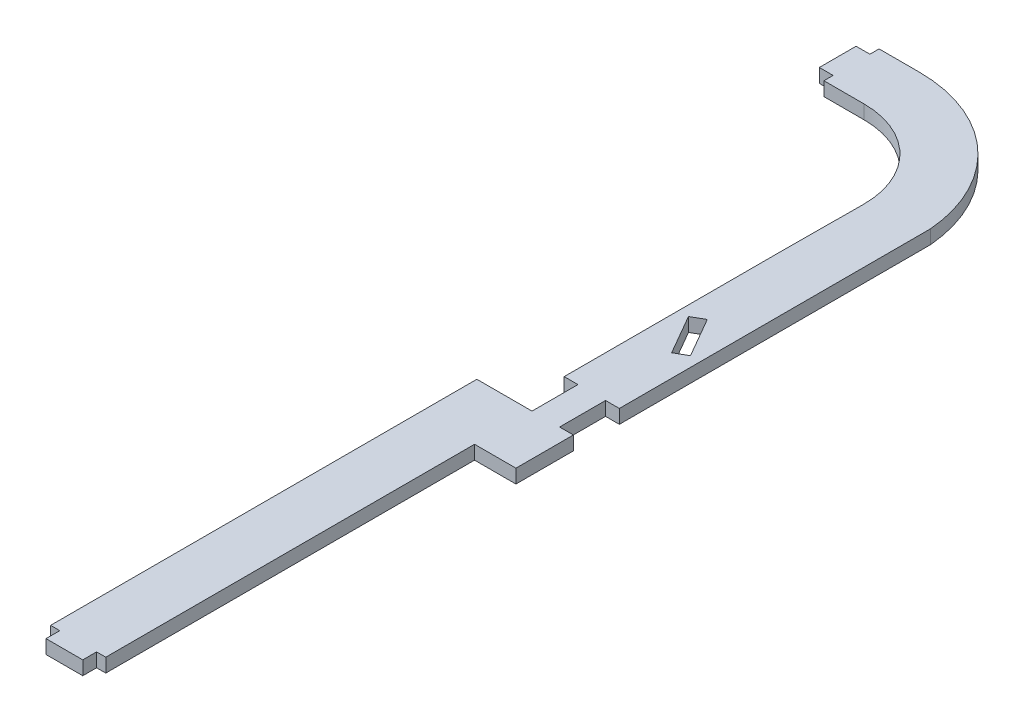
SolidWorks part; units mm, degrees
ref_plane "Alzado" through (0, 0, 0) normal (0, 0, 1) x (1, 0, 0)
ref_plane "Planta" through (0, 0, 0) normal (0, 1, 0) x (1, 0, 0)
ref_plane "Vista lateral" through (0, 0, 0) normal (1, 0, 0) x (0, 0, -1)
sketch "Croquis1" plane through (0, 0, 0) normal (0, 1, 0) x (1, 0, 0)
  line L0 (37.51, 4) -> (34.51, 4)
  line L1 (34.51, 0) -> (34.51, 8)
  line L2 (34.51, 8) -> (37.51, 8)
  line L3 (37.51, 8) -> (37.51, 10)
  line L4 (77, -108.5) -> (77, -96) construction
  line L5 (72.5, 3.893) -> (72.5, -188.737) construction
  line L6 (65, -38.5334) -> (65.107, -20.8557)
  line L7 (37.51, 10) -> (46.2513, 10)
  line L8 (37.51, -2) -> (46.2513, -2)
  line L9 (37.51, 0) -> (37.51, -2)
  line L10 (56, -188.737) -> (58, -188.737)
  line L11 (77, -108.5) -> (77, -96)
  line L12 (66, -191.737) -> (58, -191.737)
  line L13 (58, -191.737) -> (58, -188.737)
  line L14 (34.51, 0) -> (37.51, 0)
  line L15 (66, -191.737) -> (66, -188.737)
  line L16 (66, -188.737) -> (68, -188.737)
  line L17 (56, -188.737) -> (56, -96)
  line L18 (77, 4) -> (37.51, 4) construction
  line L19 (71, 3.893) -> (46.2513, -20.8557) construction
  line L20 (56, -96) -> (65, -96)
  line L21 (71, -105.737) -> (71, 3.893) construction
  line L22 (77, -108.5) -> (77, -96)
  line L23 (77, -38.5334) -> (77.107, -20.8557)
  line L24 (77, 4) -> (77, -64.74)
  line L25 (77, -64.74) -> (65, -64.74) construction
  line L26 (72.299, -63.99) -> (69.701, -65.49) construction
  line L27 (73.5, -69.0701) -> (68.5, -60.4099) construction
  line L28 (69.799, -59.6599) -> (67.201, -61.1599)
  line L29 (67.201, -61.1599) -> (72.201, -69.8201)
  line L30 (74.799, -68.3201) -> (72.201, -69.8201)
  line L31 (69.799, -59.6599) -> (74.799, -68.3201)
  line L32 (77, 4) -> (77, -86)
  line L33 (77, -96) -> (77, -108.5)
  line L34 (77, -86) -> (74, -86)
  line L35 (74, -86) -> (74, -96)
  line L36 (74, -96) -> (77, -96)
  line L37 (68, -96) -> (65, -96)
  line L38 (68, -86) -> (68, -96)
  line L39 (65, -86) -> (68, -86)
  line L40 (65, -86) -> (65, -38.5334)
  line L41 (77, -86) -> (77, 4) construction
  line L42 (77, -86) -> (77, -38.5334)
  line L43 (77, -86) -> (77, -38.5334)
  line L44 (77, -108.5) -> (68, -108.5)
  line L45 (68, -108.5) -> (68, -188.737)
  arc A0 (65.1056, -21.0838) -> (46.2513, -2) centre (46.2513, -20.8557) ccw
  arc A2 (77, -23.4225) -> (46.2513, 10) centre (46.2513, -20.8557) ccw
  point P39 (71, -64.74)
  dimension "D1" = 3
  dimension "D2" = 4
  dimension "D3" = 39.49
  dimension "D4" = 35
  dimension "D5" = 192.63
  dimension "D6" = 2
  dimension "D7" = 68.74
  dimension "D8" = 30
  dimension "D9" = 12.5
  dimension "D10" = 1.5
  dimension "D11" = 5
  dimension "D12" = 9
  dimension "D13" = 3
  dimension "D14" = 10
extrude "Saliente-Extruir1" add sketch "Croquis1" along normal blind 3 contours L22 region at (36.5716, 0, -2)
